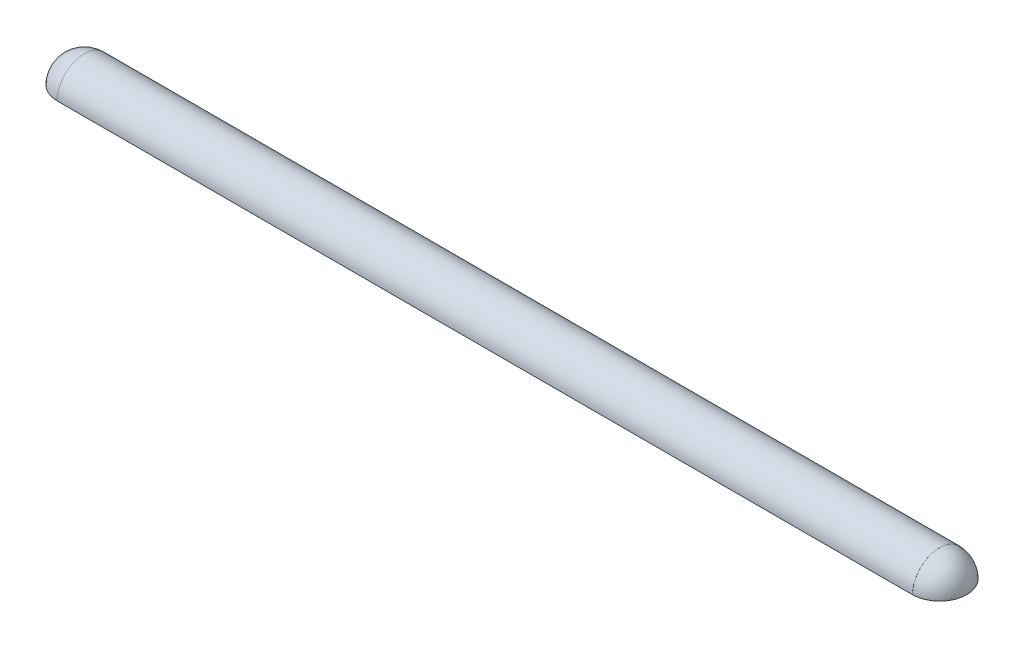
SolidWorks part; units mm, degrees
ref_plane "Front Plane" through (0, 0, 0) normal (0, 0, 1) x (1, 0, 0)
ref_plane "Top Plane" through (0, 0, 0) normal (0, 1, 0) x (1, 0, 0)
ref_plane "Right Plane" through (0, 0, 0) normal (1, 0, 0) x (0, 0, -1)
sketch "Sketch5" plane through (0, 0, 0) normal (1, 0, 0) x (0, 0, -1)
  ellipse E0 centre (0, 0) end of major axis (-20.701, 0) minor radius 20.6375
  dimension "D1" = 41.402
  dimension "D2" = 41.275
extrude "Boss-Extrude3" add sketch "Sketch5" along normal mid plane 650.24
sketch "Sketch6" plane through (0, 0, 0) normal (0, 0, 1) x (1, 0, 0)
  line L0 (-325.12, 20.6375) -> (-325.12, -20.6375) construction
  line L1 (-325.12, 0) -> (325.12, 0)
  line L2 (-325.12, 0) -> (-325.12, -20.6375)
  line L3 (-325.12, -20.6375) -> (325.12, -20.6375)
  line L4 (325.12, 0) -> (325.12, -20.6375)
extrude "Cut-Extrude2" cut sketch "Sketch6" against normal through all both and the other way through all
sketch "Sketch1" plane through (325.12, -325.12, 0) normal (-1, 0, 0) x (0, 1, 0)
  line L8 (325.12, 20.701) -> (325.12, -20.701) construction
  line L9 (325.12, 20.6375) -> (325.12, -20.701)
  arc A1 (325.12, -20.6375) -> (325.12, 20.6375) centre (325.12, 0) ccw
revolve "Revolve2" add sketch "Sketch1" angle 90 about L9 region at (325.12, 8.7588, 0) reverse direction yes
mirror "Mirror1" about plane through (0, 0, 0) normal (1, 0, 0) of "Revolve2"
shell "Shell1" thickness 3.175 removed face at (0, 0, 0)
